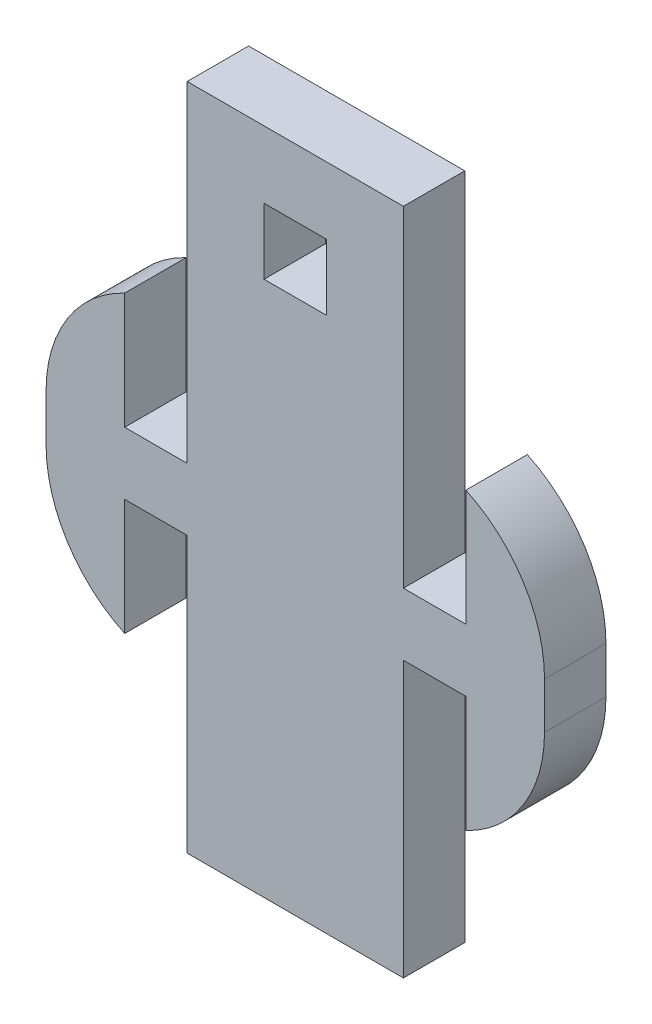
SolidWorks part; units mm, degrees
ref_plane "Front Plane" through (0, 0, 0) normal (0, 0, 1) x (1, 0, 0)
ref_plane "Top Plane" through (0, 0, 0) normal (0, 1, 0) x (1, 0, 0)
ref_plane "Right Plane" through (0, 0, 0) normal (1, 0, 0) x (0, 0, -1)
sketch "Sketch2" plane through (0, 0, 0) normal (0, 0, 1) x (1, 0, 0)
  line L0 (0, 17) -> (5.5, 17)
  line L1 (0, 17) -> (12.68, 17) construction
  line L2 (0, 17) -> (0, -17) construction
  line L3 (0, -17) -> (12.68, -17) construction
  line L4 (12.68, 17) -> (12.68, -17) construction
  line L5 (5.5, 17) -> (5.5, 0.175)
  line L6 (5.5, 0.175) -> (8.68, 0.175)
  line L7 (8.68, 0.175) -> (8.68, 6.0875)
  line L8 (8.68, 6.0875) -> (12.68, 6.0875)
  line L9 (12.68, 6.0875) -> (12.68, -8.9125)
  line L10 (12.68, -8.9125) -> (8.68, -8.9125)
  line L11 (8.68, -8.9125) -> (8.68, -3)
  line L12 (8.68, -3) -> (5.5, -3)
  line L13 (5.5, -3) -> (5.5, -17)
  line L14 (5.5, -17) -> (0, -17)
  line L15 (0, 17) -> (0, 13.59)
  line L16 (0, 13.59) -> (1.59, 13.59)
  line L17 (1.59, 13.59) -> (1.59, 10.2412)
  line L18 (1.59, 10.2412) -> (0, 10.2412)
  line L19 (0, 10.2412) -> (0, -17)
  point P0 (44.9617, 22.388)
  point P5 (12.68, -9.9245)
  point P7 (0, 0)
  point P22 (0, 0)
  dimension "D1" = 34
  dimension "D2" = 12.68
  dimension "D3" = 5.5
  dimension "D4" = 3.18
  dimension "D5" = 14
  dimension "D6" = 16.825
  dimension "D7" = 3.91
  dimension "D8" = 3.41
  dimension "D9" = 15
extrude "Boss-Extrude1" add sketch "Sketch2" along normal blind 3.125
mirror "Mirror1" about plane through (0, 10.2412, 3.125) normal (1, 0, 0) of "Boss-Extrude1"
fillet "Fillet1" radius 7 4 edges at (-12.68, -8.9125, 1.5625) (-12.68, 6.0875, 1.5625) (12.68, -8.9125, 1.5625) (12.68, 6.0875, 1.5625)
